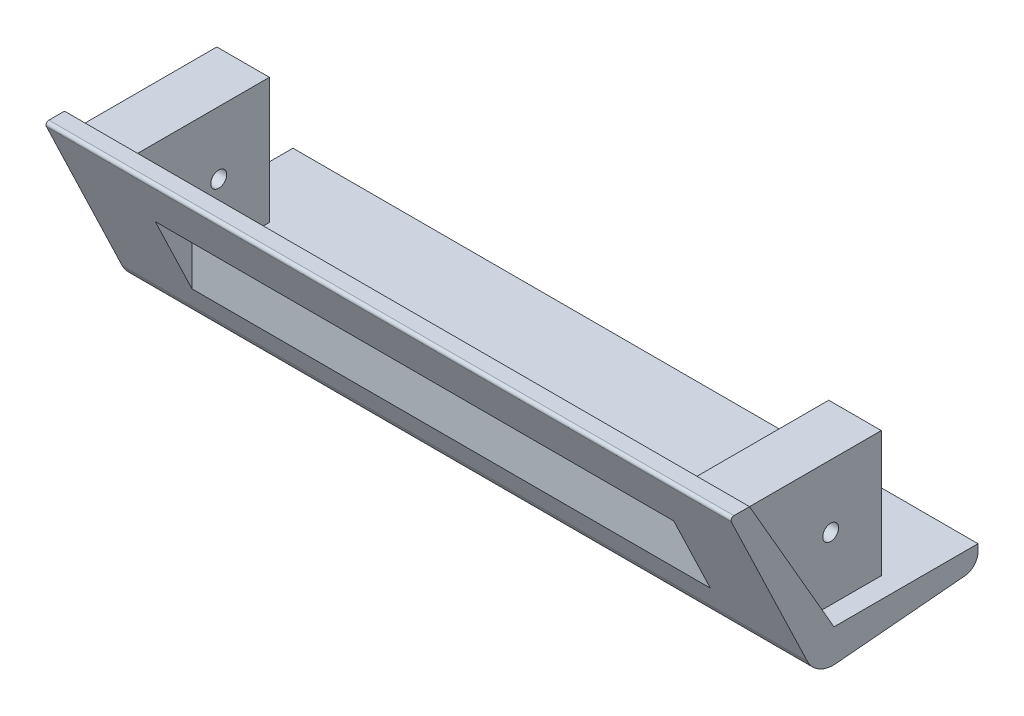
SolidWorks part; units mm, degrees
ref_plane "Front Plane" through (0, 0, 0) normal (0, 0, 1) x (1, 0, 0)
ref_plane "Top Plane" through (0, 0, 0) normal (0, 1, 0) x (1, 0, 0)
ref_plane "Right Plane" through (0, 0, 0) normal (1, 0, 0) x (0, 0, -1)
sketch "Sketch1" plane through (0, 0, 0) normal (1, 0, 0) x (0, 0, -1)
  line L0 (0, 0) -> (-29.3294, 50.8)
  line L1 (0, 0) -> (50, 0)
  line L2 (-29.3294, 50.8) -> (-36.3294, 50.8)
  line L3 (-36.3294, 50.8) -> (-6.2529, -12)
  line L4 (-6.2529, -12) -> (50, -7)
  line L5 (50, -7) -> (50, 0)
  line L6 (-6.2529, -12) -> (-6.2529, 0) construction
  line L7 (-12, 0) -> (0, 0) construction
  dimension "D1" = 50
  dimension "D2" = 60
  dimension "D3" = 50.8
  dimension "D4" = 7
  dimension "D5" = 7
  dimension "D6" = 12
extrude "Boss-Extrude2" add sketch "Sketch1" along normal mid plane 237.85
sketch "Sketch2" plane through (0, 0, 0) normal (0, 0, 1) x (1, 0, 0)
  line L0 (0, 0) -> (0, 50.8) construction
  line L5 (115.75, 47.625) -> (96.7, 47.625) construction
  line L6 (115.75, 47.625) -> (115.75, 3.175) construction
  line L11 (115.75, 3.175) -> (96.7, 3.175) construction
  line L12 (96.7, 47.625) -> (96.7, 3.175) construction
  line L14 (115.35, 47.225) -> (115.35, 3.575)
  line L15 (115.35, 3.575) -> (97.1, 3.575)
  line L28 (97.1, 47.225) -> (97.1, 3.575)
  line L29 (115.35, 47.225) -> (97.1, 47.225)
  line L30 (-96.7, 47.625) -> (-96.7, 3.175) construction
  line L31 (-115.75, 3.175) -> (-96.7, 3.175) construction
  line L32 (-115.75, 47.625) -> (-115.75, 3.175) construction
  line L33 (-115.75, 47.625) -> (-96.7, 47.625) construction
  line L34 (-115.35, 47.225) -> (-97.1, 47.225)
  line L35 (-97.1, 47.225) -> (-97.1, 3.575)
  line L36 (-115.35, 3.575) -> (-97.1, 3.575)
  line L37 (-115.35, 47.225) -> (-115.35, 3.575)
  line L39 (118.925, 0) -> (-118.925, 0) construction
  line L40 (118.925, 50.8) -> (-118.925, 50.8) construction
  line L41 (118.925, 0) -> (118.925, 50.8) construction
  dimension "D2" = 19.05
  dimension "D3" = 44.45
  dimension "D6" = 3.175
  dimension "D4" = 3.175
  dimension "D7" = 3.175
  dimension "D1" = 193.4
  dimension "D5" = 0.4
extrude "Boss-Extrude1" add sketch "Sketch2" along normal up to surface and the other way blind 20 up to face at (0, 25.4, 14.6647)
sketch "Sketch4" plane through (0, 0, 0) normal (1, 0, 0) x (0, 0, -1)
  line L1 (-26.7297, 30.7556) -> (-20, 34.641)
  line L2 (-36.3294, 50.8) -> (-6.2529, -12) construction
  line L3 (0, 0) -> (-29.3294, 50.8) construction
  line L4 (-20, 34.641) -> (-14, 24.2487)
  line L5 (-14, 24.2487) -> (-14, 4.176)
  line L8 (-26.7297, 30.7556) -> (-14, 4.176)
  dimension "D1" = 12
  dimension "D2" = 14
extrude "Cut-Extrude2" cut sketch "Sketch4" against normal mid plane 180
fillet "Fillet1" radius 10 1 edges at (0, -12, 6.2529)
fillet "Fillet2" radius 5 1 edges at (0, -7, -50)
fillet "Fillet3" radius 1 1 edges at (0, 50.8, 36.3294)
hole_wizard "M5 Clearance Hole1" positions "Sketch7" profile "Sketch6" hole size "M5" standard "ANSI Metric" end condition through all
sketch "Sketch7" plane through (115.35, 0, 0) normal (1, 0, 0) x (0, 0, -1)
  line L2 (20, 47.225) -> (20, 3.575) construction
  point P0 (2.4206, 25.4)
  point P14 (20, 25.4)
  point P15 (2.4206, 25.4)
sketch "Sketch6" plane through (115.35, 25.4, -2.4206) normal (0, 1, 0) x (0, 0, -1)
  line L0 (0, 0) -> (0, 234.275)
  line L1 (0, 234.275) -> (2.75, 234.275)
  line L2 (2.75, 234.275) -> (2.75, 0)
  line L5 (2.75, 0) -> (0, 0)
  line L11 (0, -6.35) -> (0, 107.95) construction
  dimension "Thru Hole Dia." = 5.5
  dimension "Thru Hole Depth" = 234.275
equation "\"D1@Sketch2\"=187.05mm+0.25in"
